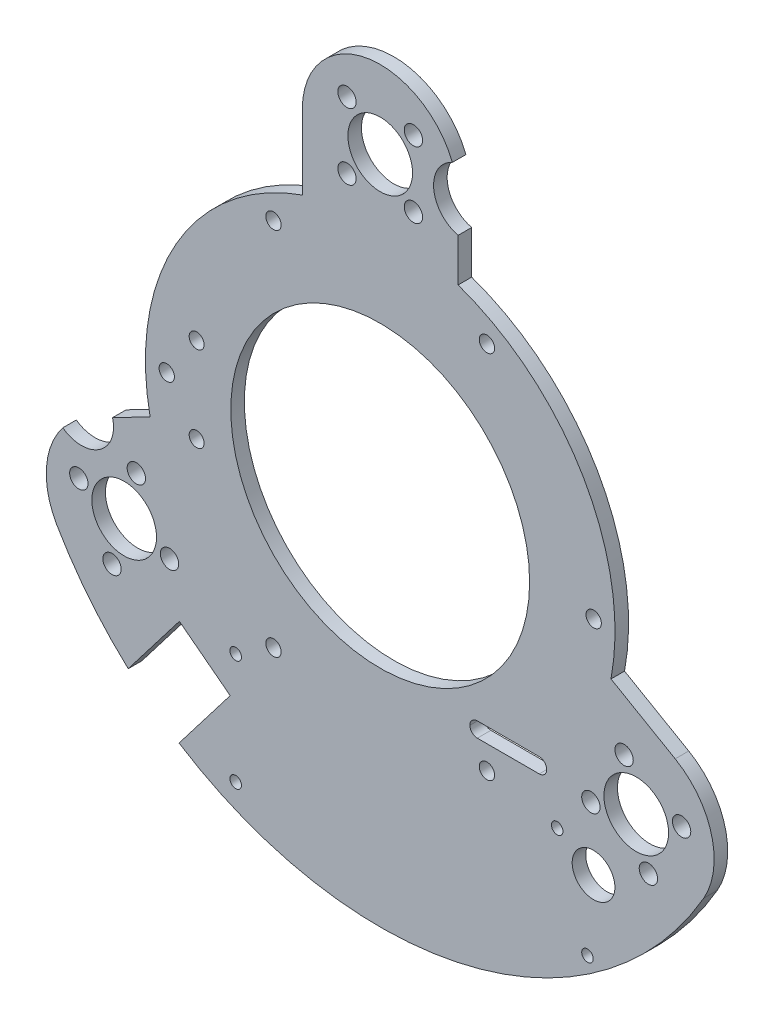
SolidWorks part; units mm, degrees
ref_plane "Front Plane" through (0, 0, 0) normal (0, 0, 1) x (1, 0, 0)
ref_plane "Top Plane" through (0, 0, 0) normal (0, 1, 0) x (1, 0, 0)
ref_plane "Right Plane" through (0, 0, 0) normal (1, 0, 0) x (0, 0, -1)
sketch "Sketch1" plane through (0, 0, 0) normal (0, 0, 1) x (1, 0, 0)
  line L0 (0, 125.7009) -> (0, -111.3832) construction
  line L1 (-141.6644, 0) -> (118.483, 0) construction
  line L2 (0, 69.25) -> (-7.7782, 77.0282) construction
  line L5 (69.0973, -18.82) -> (54.0578, -10.137)
  line L8 (-69.0973, -18.82) -> (-53.8993, -10.9483)
  line L11 (19.8875, 69.25) -> (-21.4021, 69.25) construction
  line L12 (-18.25, 69.25) -> (-18.25, 51.8839)
  line L14 (18.25, 69.25) -> (18.25, 51.8839)
  arc A0 (-75.7772, -43.75) -> (75.7772, -43.75) centre (0, 0) ccw
  circle A18 centre (-7.7782, 77.0282) radius 2.15
  arc A31 (-18.25, 51.8839) -> (-53.8993, -10.9483) centre (0, 0) ccw
  circle A32 centre (0, 0) radius 35
  arc A33 (75.7772, -43.75) -> (69.0973, -18.82) centre (59.9723, -34.625) ccw
  arc A34 (-69.0973, -18.82) -> (-75.7772, -43.75) centre (-59.9723, -34.625) ccw
  arc A36 (54.0578, -10.137) -> (18.25, 51.8839) centre (0, 0) ccw
  circle A38 centre (-50, 0) radius 1.8
  circle A39 centre (-25, 43.3013) radius 1.8
  circle A40 centre (25, 43.3013) radius 1.8
  circle A41 centre (50, 0) radius 1.8
  circle A42 centre (25, -43.3013) radius 1.8
  circle A43 centre (-25, -43.3013) radius 1.8
  arc A44 (18.25, 69.25) -> (-18.25, 69.25) centre (0, 69.25) ccw
  circle A45 centre (7.7782, 77.0282) radius 2.15
  circle A46 centre (7.7782, 61.4718) radius 2.15
  circle A47 centre (-7.7782, 61.4718) radius 2.15
  circle A49 centre (62.8193, -45.2502) radius 2.15
  circle A50 centre (49.3471, -37.472) radius 2.15
  circle A51 centre (57.1252, -23.9998) radius 2.15
  circle A52 centre (70.5974, -31.778) radius 2.15
  circle A54 centre (-70.5974, -31.778) radius 2.15
  circle A55 centre (-57.1252, -23.9998) radius 2.15
  circle A56 centre (-49.3471, -37.472) radius 2.15
  circle A57 centre (-62.8193, -45.2502) radius 2.15
  circle A58 centre (0, 69.25) radius 7.575
  circle A59 centre (59.9723, -34.625) radius 7.575
  circle A60 centre (-59.9723, -34.625) radius 7.575
  point P21 (0, 72.5)
  point P28 (0, 69.25)
  point P40 (0, 0)
  point P41 (0, 0)
  point P42 (0, 72.5)
  point P44 (0, 0)
  point P59 (0, 0)
  point P73 (0, 0)
  point P78 (0, 0)
  dimension "D1" = 175
  dimension "D2" = 70
  dimension "D3" = 18.25
  dimension "D4" = 15.15
  dimension "D5" = 4.3
  dimension "D6" = 11
  dimension "D7" = 3
  dimension "D12" = 110
  dimension "D13" = 3.6
  dimension "D11" = 69.25
  dimension "D8" = 50
  dimension "D15" = 6
  dimension "D9" = 4
  dimension "D10" = 3
extrude "Boss-Extrude1" add sketch "Sketch1" along normal blind 3.175
sketch "Sketch2" plane through (0, 0, 3.175) normal (0, 0, 1) x (1, 0, 0)
  line L0 (0, 93.7487) -> (0, -92.817) construction
  line L1 (-91.7689, 0) -> (95.9614, 0) construction
  line L2 (-35.5093, -64) -> (51.1666, -64) construction
  line L3 (-24, -49) -> (32, -49)
  line L4 (-24, -49) -> (-24, -79)
  line L5 (-24, -79) -> (32, -79)
  line L6 (32, -49) -> (32, -79)
  line L7 (-23.1064, -11.067) -> (5.3725, -70.527)
  line L8 (21.835, -39.1033) -> (32.0072, -56.3108)
  line L9 (0, 0) -> (-23.1064, -11.067) construction
  line L10 (0, 0) -> (25.3854, -3.459) construction
  line L11 (5.3725, -70.527) -> (19, -64) construction
  line L12 (19, -64) -> (32.0072, -56.3108) construction
  line L13 (-19.7204, -33) -> (34.8807, -33) construction
  line L14 (27, -18.9627) -> (27, -48.8294) construction
  line L15 (21, -34.3) -> (39, -34.3)
  line L16 (21, -34.3) -> (21, -37.8)
  line L17 (21, -37.8) -> (39, -37.8)
  line L18 (39, -34.3) -> (39, -37.8)
  line L19 (20.4704, -36.05) -> (41.1675, -36.05) construction
  line L20 (22.7, -29.2) -> (37.3, -29.2)
  line L21 (21, -30.9) -> (21, -31.1)
  line L22 (22.7, -32.8) -> (37.3, -32.8)
  line L23 (39, -30.9) -> (39, -31.1)
  line L24 (-29.2, -43.9) -> (32, -43.9)
  line L25 (-29.2, -43.9) -> (-29.2, -84.1)
  line L26 (-29.2, -84.1) -> (32, -84.1)
  line L27 (32, -43.9) -> (32, -84.1)
  line L28 (25.3854, -3.459) -> (21.0549, -35.2399)
  line L29 (27, -36.05) -> (21.0549, -35.2399) construction
  line L30 (27, -36.05) -> (21.835, -39.1033) construction
  circle A0 centre (23, -81.3) radius 1.35
  circle A1 centre (1, -81.3) radius 1.35
  circle A2 centre (-21, -81.3) radius 1.35
  circle A3 centre (-26.3, -75) radius 1.35
  circle A4 centre (23, -46.7) radius 1.35
  circle A5 centre (1, -46.7) radius 1.35
  circle A6 centre (-21, -46.7) radius 1.35
  circle A7 centre (-26.3, -53) radius 1.35
  circle A8 centre (19, -64) radius 15.11
  circle A9 centre (0, 0) radius 25.62
  circle A10 centre (19, -64) radius 18.5
  arc A13 (21, -30.9) -> (22.7, -29.2) centre (22.7, -30.9) cw
  arc A14 (37.3, -29.2) -> (39, -30.9) centre (37.3, -30.9) cw
  arc A15 (39, -31.1) -> (37.3, -32.8) centre (37.3, -31.1) cw
  arc A16 (22.7, -32.8) -> (21, -31.1) centre (22.7, -31.1) cw
  circle A18 centre (27, -36.05) radius 6
  circle A19 centre (27, -36.05) radius 2.5
  point P47 (21, -36.05)
  point P56 (39, -29.2)
  point P59 (39, -32.8)
  dimension "D4" = 2.7
  dimension "D5" = 9
  dimension "D8" = 2.7
  dimension "D9" = 22
  dimension "D10" = 2.7
  dimension "D11" = 22
  dimension "D12" = 2.7
  dimension "D14" = 58.3
  dimension "D16" = 30.22
  dimension "D17" = 13
  dimension "D18" = 51.24
  dimension "D19" = 37
  dimension "D21" = 5
  dimension "D23" = 1.75
  dimension "D33" = 1.7
  dimension "D34" = 1.7
  dimension "D41" = 12
  dimension "D22" = 3.05
  dimension "D1" = 56
  dimension "D2" = 30
  dimension "D3" = 32
  dimension "D6" = 15
  dimension "D7" = 17.3
  dimension "D13" = 11
  dimension "D15" = 64
  dimension "D20" = 33
  dimension "D25" = 3.5
  dimension "D26" = 27
  dimension "D27" = 6
  dimension "D28" = 12
  dimension "D29" = 3.6
  dimension "D30" = 0.2
  dimension "D31" = 6
  dimension "D32" = 12
  dimension "D36" = 61.2
  dimension "D37" = 40.2
  dimension "D38" = 32
  dimension "D39" = 20.1
sketch "Sketch3" plane through (0, 0, 3.175) normal (0, 0, 1) x (1, 0, 0)
  line L0 (0, 114.667) -> (0, -151.2625) construction
  line L1 (-165.5829, 0) -> (141.148, 0) construction
  line L2 (-42.6786, -64) -> (79.4842, -64) construction
  line L3 (-31.6, -36.5487) -> (-31.6, -93.553) construction
  line L4 (1, -42.7749) -> (1, -93.553) construction
  line L7 (21, -34.3) -> (21, -37.8) construction
  line L8 (21, -37.8) -> (39, -37.8) construction
  line L9 (39, -34.3) -> (39, -37.8) construction
  line L10 (21, -34.3) -> (39, -34.3) construction
  line L15 (21, -34.3) -> (21, -37.8)
  line L16 (21, -37.8) -> (39, -37.8)
  line L17 (39, -34.3) -> (39, -37.8)
  line L18 (21, -34.3) -> (39, -34.3)
  line L19 (59.9723, -34.625) -> (0, 0) construction
  line L20 (59.9723, -34.625) -> (40.6845, -68.0323) construction
  circle A6 centre (-33.85, -49) radius 1.35
  circle A7 centre (-33.85, -75) radius 1.35
  circle A8 centre (41.45, -46.7) radius 1.35
  circle A19 centre (49.9723, -51.9455) radius 5
  circle A20 centre (48.55, -69) radius 1.35
  dimension "D2" = 47.55
  dimension "D3" = 34.85
  dimension "D4" = 2.7
  dimension "D5" = 2.7
  dimension "D8" = 34.85
  dimension "D11" = 40.45
  dimension "D15" = 20
  dimension "D17" = 3.5
  dimension "D14" = 10
  dimension "D16" = 2.7
  dimension "D10" = 5
  dimension "D9" = 2.7
  dimension "D12" = 17.3
  dimension "D1" = 64
  dimension "D6" = 15
  dimension "D7" = 11
  dimension "D13" = 90
  dimension "D18" = 32.6
extrude "Cut-Extrude1" cut sketch "Sketch3" against normal blind 3.175
sketch "Sketch4" plane through (0, 0, 3.175) normal (0, 0, 1) x (1, 0, 0)
  line L0 (0, 99.8873) -> (0, -108.3836) construction
  line L1 (-110.578, 0) -> (106.2745, 0) construction
  line L2 (72.5, 85.3655) -> (72.5, -73.9916) construction
  line L15 (-18.902, 65.232) -> (-24.6423, 79.0902)
  line L16 (-47.0415, -48.9856) -> (-56.173, -60.8859)
  line L29 (0, 0) -> (-45.6571, -59.5015) construction
  line L34 (-44.2727, -70.0174) -> (-35.1412, -58.1171)
  line L35 (-35.1412, -58.1171) -> (-47.0415, -48.9856)
  line L36 (-24.6423, 79.0902) -> (-38.5005, 73.3499)
  line L37 (-38.5005, 73.3499) -> (-32.7602, 59.4917)
  line L38 (-32.7602, 59.4917) -> (-18.902, 65.232)
  line L39 (65.9436, -16.2464) -> (80.8153, -18.2042)
  line L40 (80.8153, -18.2042) -> (82.7731, -3.3326)
  line L41 (82.7731, -3.3326) -> (67.9015, -1.3747)
  line L42 (67.9015, -1.3747) -> (65.9436, -16.2464)
  line L43 (-44.2727, -70.0174) -> (-51.6073, -79.576)
  line L44 (-51.6073, -79.576) -> (-63.5076, -70.4446)
  line L45 (-63.5076, -70.4446) -> (-56.173, -60.8859)
  line L47 (-50.2228, -65.4517) -> (-44.2727, -70.0174) [skipped]
  circle A4 centre (-45.6571, -59.5015) radius 7.5 construction
  point P23 (0, 0)
  point P27 (0, 0)
  point P33 (0, 0)
  dimension "D1" = 52.5
  dimension "D5" = 72.5
  dimension "D7" = 3
  dimension "D3" = 15
  dimension "D4" = 90
  dimension "D2" = 75
extrude "Cut-Extrude2" cut sketch "Sketch4" against normal blind 3.175
sketch "Sketch6" plane through (0, 0, 0) normal (0, 0, 1) x (1, 0, 0)
  line L0 (-30.4163, 69.25) -> (44.9572, 69.25) construction
  circle A0 centre (20, 69.25) radius 7.5
  circle A1 centre (0, 69.25) radius 7.575 construction
  circle A2 centre (-69.9723, -17.3045) radius 7.5
  point P11 (0, 0)
  dimension "D2" = 15
  dimension "D3" = 20
  dimension "D1" = 69.25
  dimension "D4" = 2
extrude "Cut-Extrude5" cut sketch "Sketch6" along normal blind 10
fillet "Fillet1" radius 1.75 4 edges at (21, -37.8, 1.5875) (39, -37.8, 1.5875) (39, -34.3, 1.5875) (21, -34.3, 1.5875)
sketch "Sketch7" plane through (0, 0, 3.175) normal (0, 0, 1) x (1, 0, 0)
  line L0 (-70.8021, 0) -> (80.7932, 0) construction
  line L1 (0, 117.4664) -> (0, -108.5041) construction
  line L2 (-43, 51.6117) -> (-43, -30.4827) construction
  line L7 (-59.7154, 10) -> (-19.0015, 10) construction
  circle A1 centre (-43, 10) radius 1.75
  circle A2 centre (-43, -10) radius 1.75
  dimension "D2" = 3.5
  dimension "D1" = 10
  dimension "D5" = 43
extrude "Cut-Extrude6" cut sketch "Sketch7" against normal blind 10
sketch "Sketch8" plane through (0, 0, 3.175) normal (0, 0, 1) x (1, 0, 0)
  circle A0 centre (0, 0) radius 48
  dimension "D1" = 96
sketch "Sketch9" plane through (0, 0, 0) normal (0, 0, 1) x (1, 0, 0)
  line L0 (-35.5093, -64) -> (51.1666, -64) construction
  line L1 (-35.5093, -64) -> (51.1666, -64)
  point P2 (19, -64)
